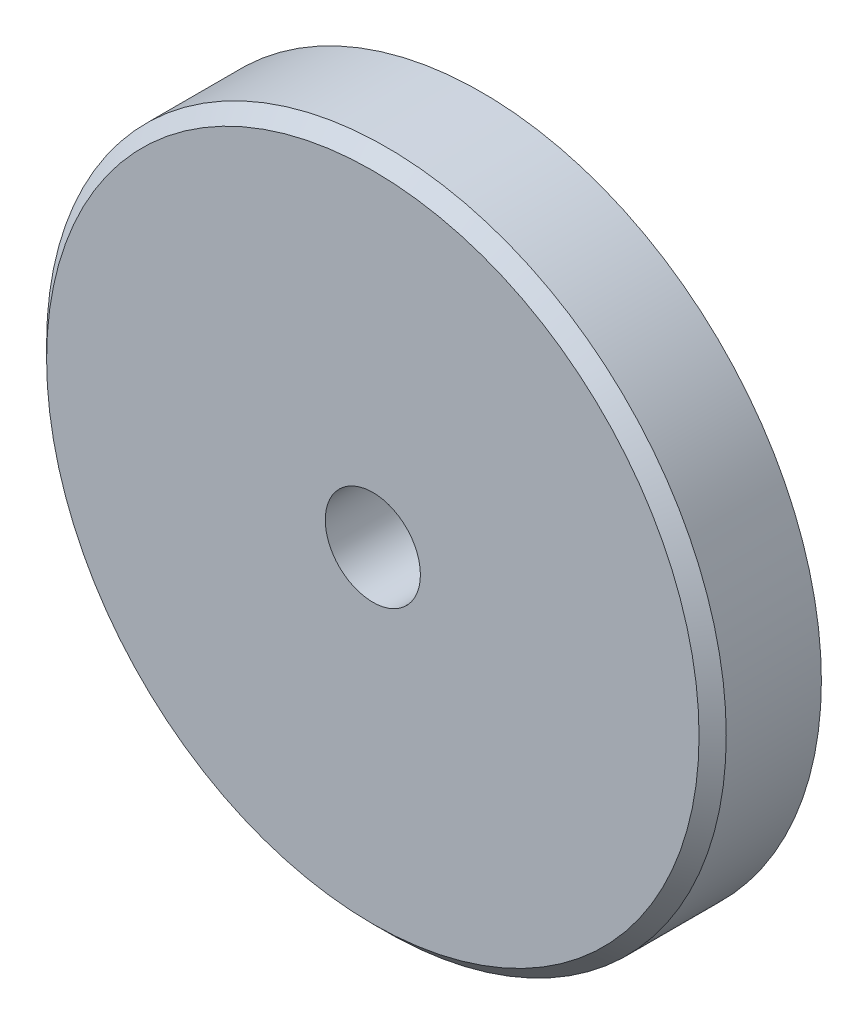
SolidWorks part; units mm, degrees
ref_plane "Front Plane" through (0, 0, 0) normal (0, 0, 1) x (1, 0, 0)
ref_plane "Top Plane" through (0, 0, 0) normal (0, 1, 0) x (1, 0, 0)
ref_plane "Right Plane" through (0, 0, 0) normal (1, 0, 0) x (0, 0, -1)
sketch "Sketch1" plane through (0, 0, 0) normal (0, 0, 1) x (1, 0, 0)
  circle A0 centre (0, 0) radius 12.5
  dimension "D1" = 25
extrude "Boss-Extrude1" add sketch "Sketch1" along normal blind 4
ref_axis "Axis1" through (0, 0, -0.35) along (0, 0, 1)
chamfer "Chamfer1" distance 0.5 angle 45 1 edges at (12.5, 0, 4)
ref_axis "Axis2" through (0, 14.0125, 4) along (0, -1, 0)
sketch "Sketch6" plane through (0, 0, 0) normal (1, 0, 0) x (0, 0, -1)
  line L0 (-4, 14.0125) -> (-4, -13.7625) construction
  line L1 (-4, 8.9) -> (-4, 11.1)
  line L2 (0, 12.5) -> (-3.5, 12.5) construction
  arc A0 (-4, 11.1) -> (-4, 8.9) centre (-4, 10) ccw
  dimension "D1" = 2.2
  dimension "D2" = 2.5
revolve "Cut-Revolve2" [suppressed] cut sketch "Sketch6" angle 360 about L1
pattern_circular "CirPattern1" [suppressed] count 15 over 360 of bodies 112
sketch "Sketch7" plane through (0, 0, 4) normal (0, 0, 1) x (1, 0, 0)
  circle A0 centre (0, 0) radius 1.25
  dimension "D1" = 2.5
extrude "Cut-Extrude1" cut sketch "Sketch7" against normal through all
sketch "Sketch10" plane through (0, 0, 4) normal (0, 0, 1) x (1, 0, 0)
  circle A0 centre (0, 0) radius 1.75
  dimension "D1" = 3.5
extrude "Cut-Extrude2" cut sketch "Sketch10" against normal through all
